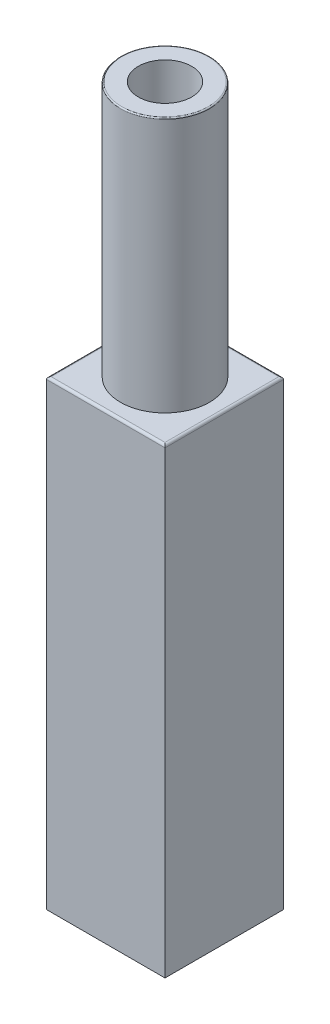
SolidWorks part; units mm, degrees
ref_plane "Front Plane" through (0, 0, 0) normal (0, 0, 1) x (1, 0, 0)
ref_plane "Top Plane" through (0, 0, 0) normal (0, 1, 0) x (1, 0, 0)
ref_plane "Right Plane" through (0, 0, 0) normal (1, 0, 0) x (0, 0, -1)
sketch "Sketch1" plane through (0, 0, 0) normal (0, 1, 0) x (1, 0, 0)
  line L5 (-50, -50) -> (50, -50)
  line L6 (-50, -50) -> (-50, 50)
  line L7 (-50, 50) -> (50, 50)
  line L8 (50, -50) -> (50, 50)
  line L9 (-50, -50) -> (50, 50) construction
  line L10 (-50, 50) -> (50, -50) construction
  circle A0 centre (0, 0) radius 37.5
  circle A1 centre (0, 0) radius 22.5
  dimension "D3" = 75
  dimension "D4" = 45
  dimension "D1" = 100
  dimension "D2" = 100
extrude "Boss-Extrude2" add sketch "Sketch1" along normal blind 150 and the other way blind 239.2462 contours L6 L7 L8 L5
extrude "Boss-Extrude3" add sketch "Sketch1<4>" along normal blind 365.5285 separate body contours A0 | A1
sketch "Sketch1<4>" plane through (0, 0, 0) normal (0, 1, 0) x (1, 0, 0) same geometry as "Sketch1"
extrude "Cut-Extrude1" cut sketch "Sketch1<5>" along normal blind 215 contours A1 region at (0, 0, 0)
sketch "Sketch1<5>" plane through (0, 0, 0) normal (0, 1, 0) x (1, 0, 0) same geometry as "Sketch1"
fillet "Fillet2" radius 2 4 edges at (-50, 150, 0) (0, 150, 50) (50, 150, 0) (0, 150, -50)
fillet "Fillet3" radius 1 1 edges at (0, 365.5285, 37.5)
